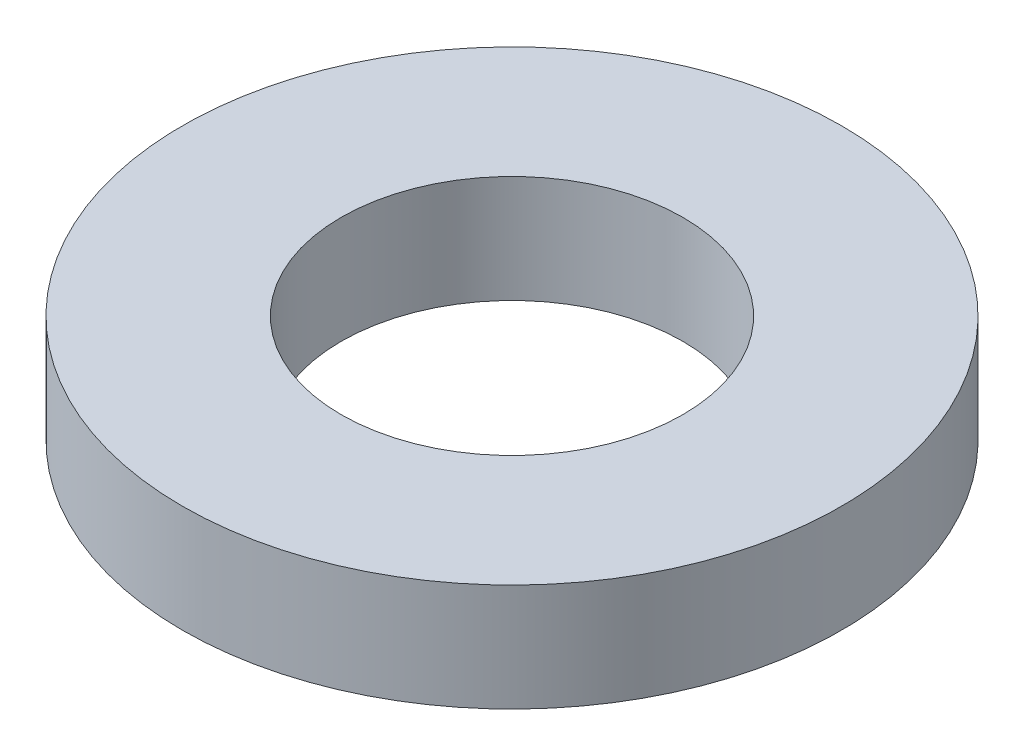
SolidWorks part; units mm, degrees
ref_plane "Front Plane" through (0, 0, 0) normal (0, 0, 1) x (1, 0, 0)
ref_plane "Top Plane" through (0, 0, 0) normal (0, 1, 0) x (1, 0, 0)
ref_plane "Right Plane" through (0, 0, 0) normal (1, 0, 0) x (0, 0, -1)
sketch "Sketch1" plane through (0, 0, 0) normal (0, 1, 0) x (1, 0, 0)
  circle A0 centre (0, 0) radius 67.5
  dimension "FLANGE_OD" = 135
extrude "Boss-Extrude1" add sketch "Sketch1" along normal blind 22
sketch "Sketch2" plane through (0, 0, 0) normal (0, 1, 0) x (1, 0, 0)
  circle A0 centre (0, 0) radius 35
  dimension "BORE_D" = 70
extrude "Cut-Extrude1" cut sketch "Sketch2" along normal through all
sketch "Sketch3" plane through (0, 22, 0) normal (0, 1, 0) x (1, 0, 0)
  circle A0 centre (0, 0) radius 24.2239 construction
  circle A1 centre (-24.2239, 0) radius 2.2711
  dimension "BOLT_D" = 4.5422
  dimension "BOLT_PCD" = 48.4478
extrude "Cut-Extrude2" cut sketch "Sketch3" against normal blind 16.9635 rebuild error yes
pattern_circular "CirPattern1" count 6 over 360 rebuild error yes
